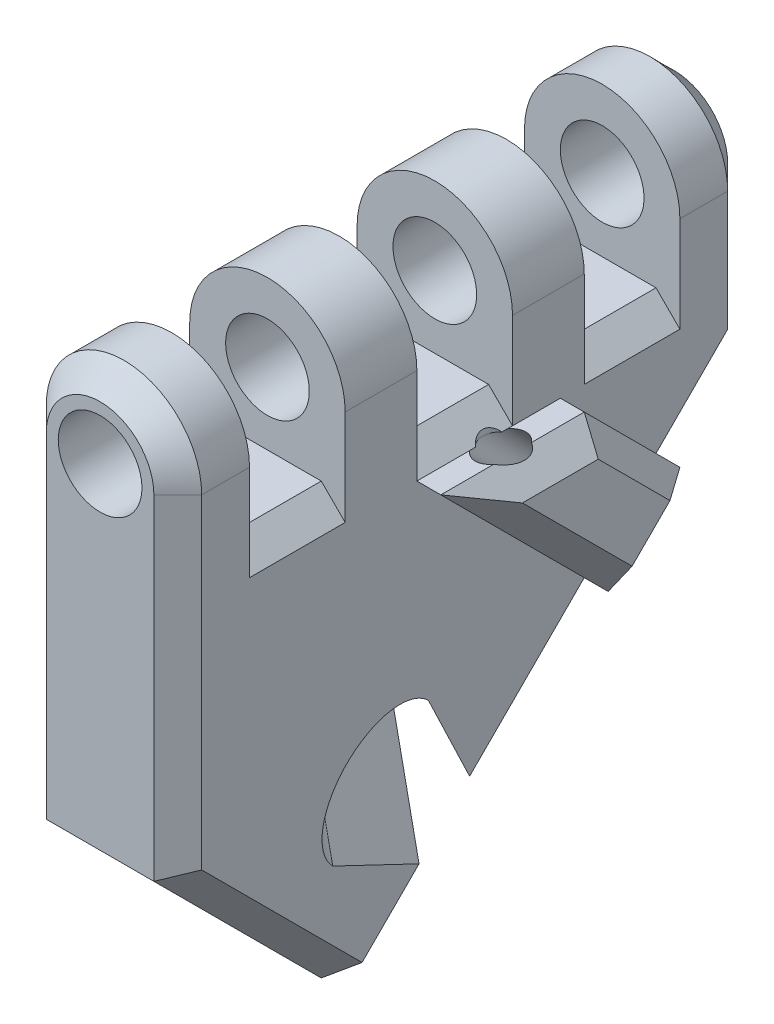
SolidWorks part; units mm, degrees
ref_plane "Front Plane" through (0, 0, 0) normal (0, 0, 1) x (1, 0, 0)
ref_plane "Top Plane" through (0, 0, 0) normal (0, 1, 0) x (1, 0, 0)
ref_plane "Right Plane" through (0, 0, 0) normal (1, 0, 0) x (0, 0, -1)
sketch "Sketch1" plane through (0, 0, 0) normal (0, 0, 1) x (1, 0, 0)
  line L0 (0, 0) -> (0, -28) construction
  line L1 (3.25, 0) -> (0, 0) construction
  line L2 (-3.25, 0) -> (-3.25, -28)
  line L3 (-3.25, -28) -> (3.25, -28)
  line L4 (3.25, 0) -> (3.25, -28)
  line L5 (0, 0) -> (-3.25, 0) construction
  arc A0 (-3.25, 0) -> (3.25, 0) centre (0, 0) cw
  dimension "D1" = 6.5
  dimension "D2" = 28
extrude "Boss-Extrude1" add sketch "Sketch1" along normal blind 24
sketch "Sketch2" plane through (0, 0, 0) normal (0, 0, -1) x (-1, 0, 0)
  circle A0 centre (0, 0) radius 1.75
  arc A1 (3.25, 0) -> (-3.25, 0) centre (0, 0) ccw construction
  dimension "D1" = 3.5
extrude "Cut-Extrude1" cut sketch "Sketch2" against normal up to surface (24 mm away) up to face at (0, -13.1875, 24)
sketch "Sketch3" plane through (-3.25, 0, 0) normal (-1, 0, 0) x (0, 0, 1)
  line L0 (0, 3.25) -> (0, 0) construction
  line L1 (3, -3) -> (7, -3)
  line L2 (3, -3) -> (3, 4)
  line L3 (3, 4) -> (7, 4)
  line L4 (7, -3) -> (7, 4)
  line L5 (17, -3) -> (21, -3)
  line L6 (17, -3) -> (17, 4)
  line L7 (17, 4) -> (21, 4)
  line L8 (21, -3) -> (21, 4)
  line L9 (24, 0) -> (0, 0) construction
  line L10 (7, 4) -> (10, 4) construction
  line L11 (10, -3) -> (14, -3)
  line L12 (10, -3) -> (10, 4)
  line L13 (24, 0) -> (24, -28) construction
  line L14 (10, 4) -> (14, 4)
  line L15 (14, -3) -> (14, 4)
  line L16 (14, 4) -> (17, 4) construction
  dimension "D1" = 3
  dimension "D2" = 3
  dimension "D3" = 4
  dimension "D4" = 3
  dimension "D5" = 4
extrude "Cut-Extrude2" cut sketch "Sketch3" against normal up to surface (6.5 mm away) up to face at (3.25, -14, 12)
chamfer "Chamfer1" distance 1 angle 45 6 edges at (3.25, -3, 19) (3.25, -3, 5) (-3.25, -3, 19) (-3.25, -3, 5) (3.25, -3, 12) (-3.25, -3, 12)
sketch "Sketch7" plane through (-3.25, 0, 0) normal (-1, 0, 0) x (0, 0, 1)
  line L0 (24, -28) -> (0, -4)
  line L1 (0, 0) -> (0, -28) construction
  line L2 (0, -4) -> (0, -28)
  line L3 (0, -28) -> (24, -28)
  line L4 (7, -4) -> (3, -4) construction
extrude "Cut-Extrude4" cut sketch "Sketch7" against normal up to next
sketch "Sketch10" plane through (3.25, 0, 0) normal (1, 0, 0) x (0, 0, -1)
  line L0 (-24, -14) -> (-17, -21)
  line L1 (-24, -28) -> (-24, 0) construction
  line L2 (0, -4) -> (-24, -28) construction
  line L3 (-17, -21) -> (-24, -28)
  line L4 (-24, -28) -> (-24, -14)
  line L5 (-24, -14) -> (-23.9648, -14.1153)
  line M1 (-24, 0) -> (-24, -28)
  line M2 (-24, -28) -> (0, -4)
extrude "Cut-Extrude5" cut sketch "Sketch10" against normal through all contours L0 M1 M2 region at (3.25, -21, 21.6667)
chamfer "Chamfer3" distance 1 angle 45 8 edges at (3.25, -2, 0) (0, 3.25, 0) (-3.25, -2, 0) (-3.25, -7, 24) (-3.25, -17.5, 20.5) (0, 3.25, 24) (3.25, -17.5, 20.5) (3.25, -7, 24)
ref_plane "Plane1" through (11.81, -8.351, 8.351) normal (-0.7071, 0.5, -0.5) x (-0.4082, 0.2887, 0.866)
sketch "Sketch18" plane through (11.81, -8.351, 8.351) normal (-0.7071, 0.5, -0.5) x (-0.4082, 0.2887, 0.866)
  line L0 (-1.9042, -2.2061) -> (6.9252, -14.6927) construction
  line L1 (8.017, -9.7069) -> (1.0914, -14.604) construction
  line L2 (6.8623, -8.0739) -> (9.1717, -11.3399) construction
  line L3 (3.4067, -13.5792) -> (2.8293, -12.7627)
  line L4 (2.8293, -12.7627) -> (6.8623, -8.0739)
  line L5 (3.4067, -13.5792) -> (9.1717, -11.3399)
  circle A0 centre (8.017, -9.7069) radius 2
  point P10 (3.118, -13.171)
  dimension "D1" = 4
  dimension "D2" = 3.77
  dimension "D3" = 1
  dimension "D4" = 6
extrude "Cut-Extrude10" cut sketch "Sketch18" against normal blind 13 and the other way blind 13 contours L5 A0 L4 | A0 L4 L3 L5 region at (2.9328, -16.431, 12.8251) region at (2.9328, -13.9602, 15.296)
sketch "Sketch11" plane through (-3.25, 0, 0) normal (-1, 0, 0) x (0, 0, 1)
  line L0 (16.2929, -20.2929) -> (9.3137, -13.3137) construction
  line L1 (10, -4) -> (14, -4)
  line L2 (10, -4) -> (10, -14)
  line L3 (10, -14) -> (14, -14)
  line L4 (14, -4) -> (14, -14)
extrude "Boss-Extrude3" add sketch "Sketch11" along normal blind 2
chamfer "Chamfer4" distance 1 angle 45 4 edges at (-5.25, -4, 12) (-5.25, -9, 14) (-5.25, -14, 12) (-5.25, -9, 10)
sketch "Sketch12" plane through (0, -4, 0) normal (0, 1, 0) x (1, 0, 0)
  line L0 (-4.25, -12) -> (-3.25, -12) construction
  line L1 (-4.25, -10) -> (-4.25, -14) construction
  line L2 (-3.25, -14) -> (-3.25, -10) construction
  line L3 (-5.25, -13) -> (-5.25, -11) construction
  circle A0 centre (-3.75, -12) radius 0.75
  dimension "D1" = 1.5
  dimension "D2" = 1.5
extrude "Cut-Extrude6" cut sketch "Sketch12" against normal blind 15 and the other way blind 2
sketch "Sketch14" plane through (3.25, 0, 0) normal (1, 0, 0) x (0, 0, -1)
  line L0 (-14, -4) -> (-7, -11)
  line L1 (-14, -4) -> (-8, -4)
  line L2 (-1, -5) -> (-11.7948, -15.7948) construction
  line L3 (-7, -11) -> (-4, -8)
  line L4 (-4, -8) -> (-8, -4)
  line L5 (-8, -4) -> (-7.959, -3.9859)
  line L6 (-7, -11) -> (-4, -8)
  line M9 (-10, -4) -> (-14, -4)
  line M26 (-11.7948, -15.7948) -> (-1, -5)
  dimension "D1" = 6
extrude "Boss-Extrude6" add sketch "Sketch14" along normal blind 2 contours L4 L0 M26 M9 region at (3.25, -6.8182, 8.4545)
chamfer "Chamfer6" distance 1 angle 45 4 edges at (5.25, -7.5, 10.5) (5.25, -4, 11) (5.25, -6, 6) (5.25, -9.5, 5.5)
sketch "Sketch19" plane through (0, -2, -2) normal (0, -0.7071, -0.7071) x (1, 0, 0)
  line L0 (4.25, 10.6066) -> (2.6167, 10.6066) construction
  line L1 (4.25, 8.4853) -> (4.25, 12.7279) construction
  line L2 (5.25, 11.7279) -> (5.25, 9.4853) construction
  circle A0 centre (3.75, 10.6066) radius 0.75
  dimension "D1" = 1.5
  dimension "D2" = 1.5
extrude "Cut-Extrude11" cut sketch "Sketch19" against normal up to surface (7.0282 mm away) up to face at (3.65, -4, 10.8)
sketch "Sketch20" plane through (0, -4, 0) normal (0, 1, 0) x (1, 0, 0)
  circle A0 centre (3.75, -11) radius 0.75
  ellipse E0 centre (3.75, -11) end of major axis (3.75, -9.9393) minor radius 0.75 (4.25, -10.2094) -> (3.25, -10.2094) ccw construction
  dimension "D1" = 1.5
extrude "Cut-Extrude12" cut sketch "Sketch20" along normal blind 1
